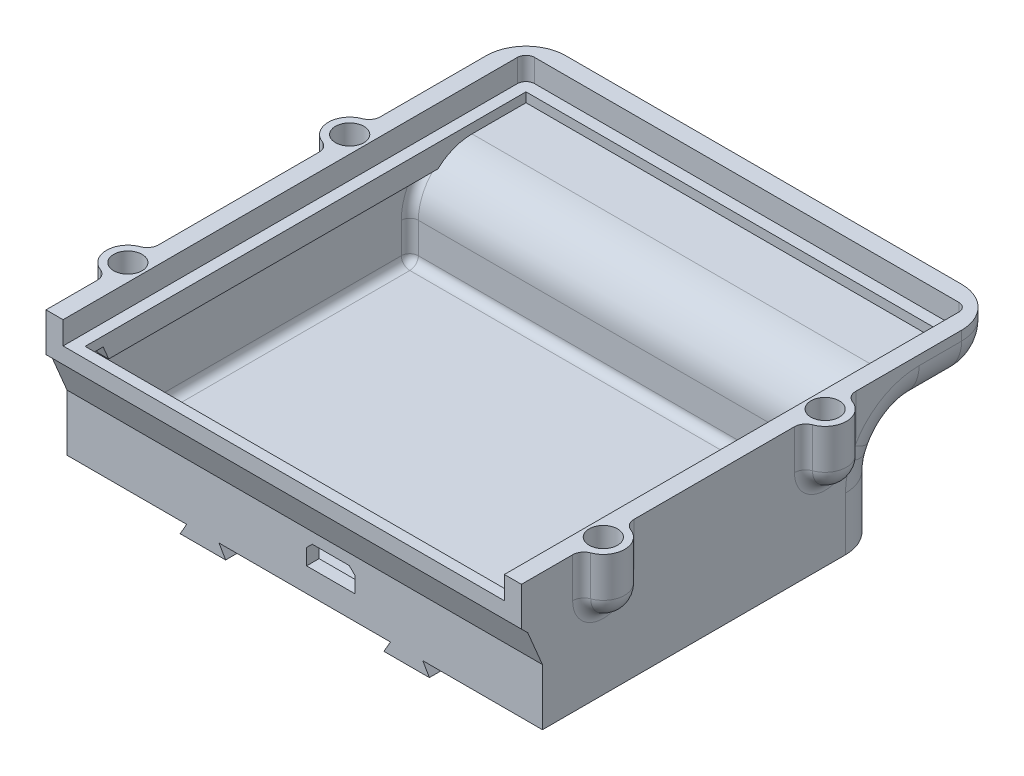
SolidWorks part; units mm, degrees
ref_plane "Front Plane" through (0, 0, 0) normal (0, 0, 1) x (1, 0, 0)
ref_plane "Top Plane" through (0, 0, 0) normal (0, 1, 0) x (1, 0, 0)
ref_plane "Right Plane" through (0, 0, 0) normal (1, 0, 0) x (0, 0, -1)
sketch "Sketch1" plane through (0, 0, 0) normal (0, 1, 0) x (1, 0, 0)
  line L4 (66, -41.25) -> (66, 44.25)
  line L5 (-66, 44.25) -> (66, 44.25)
  line L9 (-66, -41.25) -> (-66, 44.25)
  line L11 (-63, -38.25) -> (63, -38.25)
  line L12 (-66, -41.25) -> (66, -41.25)
  line L13 (-63, -38.25) -> (-63, 41.25)
  line L14 (-63, 41.25) -> (63, 41.25)
  line L15 (63, -38.25) -> (63, 41.25)
  line L16 (-63, -41.25) -> (63, 41.25) construction
  line L17 (-63, 41.25) -> (63, -41.25) construction
  line L18 (-63, -38.25) -> (63, -38.25) construction
  line L19 (-63, -41.25) -> (63, -41.25) construction
  line L20 (-66, -44.25) -> (66, -44.25) construction
  line L21 (66, -44.25) -> (66, 44.25) construction
  line L22 (63, -41.25) -> (63, 41.25) construction
  line L23 (-66, -44.25) -> (-66, 44.25) construction
  line L24 (-63, -41.25) -> (-63, 41.25) construction
  dimension "D1" = 3
  dimension "D2" = 3
  dimension "D5" = 126
  dimension "D6" = 82.5
extrude "Boss-Extrude1" add sketch "Sketch1" along normal blind 21
sketch "Sketch2" plane through (0, 0, 0) normal (0, -1, 0) x (1, 0, 0)
  line L4 (66, 41.25) -> (-66, 41.25)
  line L5 (-66, 41.25) -> (-66, -44.25)
  line L6 (-66, -44.25) -> (66, -44.25)
  line L7 (66, -44.25) -> (66, 41.25)
  line L9 (-66, 41.25) -> (-66, -44.25)
  line L10 (-66, -44.25) -> (66, -44.25)
  line L11 (66, -44.25) -> (66, 41.25)
  line L12 (66, 41.25) -> (-66, 41.25)
  dimension "D1" = 0
extrude "Boss-Extrude2" add sketch "Sketch2" along normal blind 3
sketch "Sketch3" plane through (0, 21, 0) normal (0, 1, 0) x (1, 0, 0)
  line L0 (-63, -38.25) -> (-63, -41.25)
  line L1 (-66, -41.25) -> (66, -41.25) construction
  line L2 (63, -38.25) -> (63, -41.25)
  line L3 (63, -41.25) -> (-63, -41.25)
  line L4 (-63, -38.25) -> (63, -38.25)
extrude "Cut-Extrude1" cut sketch "Sketch3" against normal blind 4
sketch "Sketch4" plane through (0, 17, 0) normal (0, 1, 0) x (1, 0, 0)
  line L0 (-61, 39.25) -> (-61, -38.25)
  line L1 (-63, 41.25) -> (63, 41.25)
  line L2 (-63, 41.25) -> (-63, -38.25)
  line L3 (-63, -38.25) -> (-61, -38.25)
  line L4 (63, 41.25) -> (63, -38.25)
  line L6 (61, 39.25) -> (61, -38.25)
  line L7 (-61, 39.25) -> (61, 39.25)
  line L8 (-61, 39.25) -> (-61, -36.25) construction
  line L9 (61, 39.25) -> (61, -36.25) construction
  line L10 (-61, -36.25) -> (61, -36.25) construction
  line L11 (61, -38.25) -> (63, -38.25)
  line L12 (-63, -38.25) -> (63, -38.25) construction
  dimension "D1" = 2
extrude "Boss-Extrude3" add sketch "Sketch4" against normal blind 4
sketch "Sketch6" plane through (0, 0, 41.25) normal (0, 0, 1) x (1, 0, 0)
  line L0 (-66, 21) -> (-66, -3) construction
  line L10 (63, 21) -> (-63, 21) construction
  line L11 (-25.5, 3.75) -> (-13.5, 3.75)
  line L12 (-25.5, 3.75) -> (-25.5, 11.25)
  line L13 (-25.5, 11.25) -> (-13.5, 11.25)
  line L14 (-13.5, 3.75) -> (-13.5, 11.25)
  line L15 (-25.5, 3.75) -> (-13.5, 11.25) construction
  line L16 (-25.5, 11.25) -> (-13.5, 3.75) construction
  line L17 (26.5, 3.75) -> (38.5, 3.75)
  line L18 (26.5, 3.75) -> (26.5, 11.25)
  line L19 (26.5, 11.25) -> (38.5, 11.25)
  line L20 (38.5, 3.75) -> (38.5, 11.25)
  line L21 (26.5, 3.75) -> (38.5, 11.25) construction
  line L22 (26.5, 11.25) -> (38.5, 3.75) construction
  line L23 (66, 21) -> (66, -3) construction
  point P11 (-19.5, 7.5)
  point P17 (32.5, 7.5)
  dimension "D1" = 12
  dimension "D2" = 7.5
  dimension "D3" = 12
  dimension "D4" = 7.5
  dimension "D5" = 46.5
  dimension "D6" = 13.5
  dimension "D7" = 13.5
  dimension "D8" = 33.5
extrude "Cut-Extrude2" cut sketch "Sketch6" against normal up to surface (3 mm away) up to face at (0, 10.75, 38.25)
sketch "Sketch7" plane through (0, 0, 41.25) normal (0, 0, 1) x (1, 0, 0)
  line L17 (0, -3) -> (0, 21) construction
  line L18 (66, -3) -> (-66, -3) construction
  line L19 (63, 21) -> (-63, 21) construction
  line L28 (-46.1132, -5) -> (-38.1132, -5)
  line L30 (-39.2679, -3) -> (-38.1132, -5)
  line L31 (-44.9585, -3) -> (-46.1132, -5)
  line L35 (39.2679, -3) -> (44.9585, -3)
  line L36 (-39.2679, -3) -> (-44.9585, -3)
  line L37 (44.9585, -3) -> (46.1132, -5)
  line L38 (39.2679, -3) -> (38.1132, -5)
  line L39 (46.1132, -5) -> (38.1132, -5)
  dimension "D1" = 8
extrude "Boss-Extrude4" add sketch "Sketch7" against normal up to surface (85.5 mm away) up to face at (0, 9, -44.25)
sketch "Sketch10" plane through (0, 21, 0) normal (0, 1, 0) x (1, 0, 0)
  line L1 (-66, -6.25) -> (66, -6.25) construction
  line L3 (0, 44.25) -> (0, -41.25) construction
  line L4 (66, 44.25) -> (-66, 44.25) construction
  line L5 (-63, -41.25) -> (63, -41.25) construction
  circle A1 centre (-66, 13.25) radius 2.5
  circle A2 centre (-66, -25.75) radius 2.5
  circle A3 centre (66, -25.75) radius 2.5
  dimension "D1" = 19.5
  dimension "D2" = 5
  dimension "D3" = 35
extrude "Cut-Extrude3" cut sketch "Sketch10" against normal blind 7
sketch "Sketch11" plane through (0, 21, 0) normal (0, 1, 0) x (1, 0, 0)
  line L0 (-66, -28.25) -> (-66, -23.25) construction
  line L1 (0, -41.25) -> (0, 44.25) construction
  line L2 (-63, -41.25) -> (63, -41.25) construction
  line L3 (66, 44.25) -> (-66, 44.25) construction
  circle A0 centre (-66, 13.25) radius 2.5
  circle A1 centre (-66, 13.25) radius 3.75
  circle A2 centre (-66, -25.75) radius 2.5
  circle A3 centre (-66, -25.75) radius 3.75
  circle A4 centre (66, -25.75) radius 3.75
  circle A5 centre (66, -25.75) radius 2.5
  dimension "D1" = 5
  dimension "D2" = 7.5
  dimension "D3" = 5
  dimension "D4" = 7.5
extrude "Boss-Extrude5" add sketch "Sketch11" against normal blind 7
sketch "Sketch13" plane through (0, 14, 0) normal (0, -1, 0) x (1, 0, 0)
  line L4 (-66, -17) -> (-66, -15.75)
  line L5 (-66, -10.75) -> (-66, -9.5)
  line L6 (-66, -17) -> (-66, -10.75)
  line L7 (-66, -10.75) -> (-66, -9.5)
  line L8 (-66, 22) -> (-66, 23.25)
  line L9 (-66, 28.25) -> (-66, 29.5)
  line L10 (-66, 22) -> (-66, 28.25)
  line L11 (-66, 28.25) -> (-66, 29.5)
  arc A4 (-66, -9.5) -> (-66, -17) centre (-66, -13.25) ccw
  arc A5 (-66, -10.75) -> (-66, -15.75) centre (-66, -13.25) ccw
  arc A6 (-66, -9.5) -> (-66, -17) centre (-66, -13.25) ccw
  arc A8 (-66, 29.5) -> (-66, 22) centre (-66, 25.75) ccw
  arc A9 (-66, 28.25) -> (-66, 23.25) centre (-66, 25.75) ccw
  arc A10 (-66, 29.5) -> (-66, 22) centre (-66, 25.75) ccw
  dimension "D1" = 0
  dimension "D2" = 0
revolve "Revolve2" add sketch "Sketch13" angle 90 about L10
sketch "Sketch14" plane through (0, 21, 0) normal (0, 1, 0) x (1, 0, 0)
  line L1 (-63, 41.25) -> (63, 41.25)
  line L2 (-63, 41.25) -> (-63, -41.25)
  line L3 (-63, -41.25) -> (63, -41.25)
  line L4 (63, 41.25) -> (63, -41.25)
extrude "Cut-Extrude4" cut sketch "Sketch14" against normal up to surface (4 mm away) up to face at (0, 17, -0.5)
sketch "Sketch17" plane through (0, 21, 0) normal (0, 1, 0) x (1, 0, 0)
  line L0 (14, 46.4113) -> (68.009, 46.4113)
  line L1 (68.009, 46.4113) -> (68.009, 34.75)
  line L4 (14, 46.4113) -> (14, 34.75)
  line L6 (14, 34.75) -> (68.009, 34.75)
extrude "Cut-Extrude5" cut sketch "Sketch17" against normal up to surface (26 mm away) up to face at (42.1132, -5, -1.5)
sketch "Sketch19" plane through (0, 14, 0) normal (0, -1, 0) x (1, 0, 0)
  line L2 (66, 23.25) -> (66, 22)
  line L3 (66, 29.5) -> (66, 28.25)
  line L4 (66, 28.25) -> (66, 22)
  line L5 (66, 29.5) -> (66, 28.25)
  arc A3 (66, 22) -> (66, 29.5) centre (66, 25.75) ccw
  arc A5 (66, 23.25) -> (66, 28.25) centre (66, 25.75) ccw
  arc A6 (66, 22) -> (66, 29.5) centre (66, 25.75) ccw
  dimension "D1" = 0
revolve "Revolve3" add sketch "Sketch19" angle 90 about L4
fillet "Fillet1" radius 2 9 edges at (66, 17.5, 22) (-66, 17.5, 22) (-66, 10.25, 25.75) (-66, 17.5, -17) (-66, 10.25, -13.25) (66, 17.5, 29.5) (-66, 17.5, 29.5) (-66, 17.5, -9.5) (66, 10.25, 25.75)
sketch "Sketch20" plane through (0, 0, 41.25) normal (0, 0, 1) x (1, 0, 0)
  line L0 (-25.5, 3.75) -> (-13.5, 3.75) construction
  line L1 (-25.5, 11.25) -> (-13.5, 11.25)
  line L2 (-25.5, 11.25) -> (-25.5, 3.75)
  line L3 (-25.5, 3.75) -> (-13.5, 3.75)
  line L4 (-13.5, 11.25) -> (-13.5, 3.75)
  line L5 (38.5, 3.75) -> (38.5, 11.25) construction
  line L6 (26.5, 11.25) -> (38.5, 11.25)
  line L7 (26.5, 11.25) -> (26.5, 3.75)
  line L8 (26.5, 3.75) -> (38.5, 3.75)
  line L9 (38.5, 11.25) -> (38.5, 3.75)
  line L16 (66, 21) -> (63, 21)
  line L17 (63, 21) -> (63, 17)
  line L18 (63, 17) -> (-63, 17)
  line L19 (-63, 17) -> (-63, 21)
  line L20 (-63, 21) -> (-66, 21)
  line L21 (-66, 21) -> (-66, -3)
  line L22 (-66, -3) -> (-44.9585, -3)
  line L23 (-44.9585, -3) -> (-46.1132, -5)
  line L24 (-46.1132, -5) -> (-38.1132, -5)
  line L25 (-38.1132, -5) -> (-39.2679, -3)
  line L26 (-39.2679, -3) -> (39.2679, -3)
  line L27 (39.2679, -3) -> (38.1132, -5)
  line L28 (38.1132, -5) -> (46.1132, -5)
  line L29 (46.1132, -5) -> (44.9585, -3)
  line L30 (44.9585, -3) -> (66, -3)
  line L31 (66, -3) -> (66, 21)
  line L32 (66, 21) -> (63, 21)
  line L33 (63, 21) -> (63, 17)
  line L34 (63, 17) -> (-63, 17)
  line L35 (-63, 17) -> (-63, 21)
  line L36 (-63, 21) -> (-66, 21)
  line L37 (-66, 21) -> (-66, -3)
  line L38 (-66, -3) -> (-44.9585, -3)
  line L39 (-44.9585, -3) -> (-46.1132, -5)
  line L40 (-46.1132, -5) -> (-38.1132, -5)
  line L41 (-38.1132, -5) -> (-39.2679, -3)
  line L42 (-39.2679, -3) -> (39.2679, -3)
  line L43 (39.2679, -3) -> (38.1132, -5)
  line L44 (38.1132, -5) -> (46.1132, -5)
  line L45 (46.1132, -5) -> (44.9585, -3)
  line L46 (44.9585, -3) -> (66, -3)
  line L47 (66, -3) -> (66, 21)
  dimension "D1" = 0
extrude "Boss-Extrude8" add sketch "Sketch20" along normal blind 2
sketch "Sketch21" plane through (0, 0, 38.25) normal (0, 0, -1) x (-1, 0, 0)
  line L1 (-38.5, 11.25) -> (-26.5, 11.25)
  line L2 (-38.5, 11.25) -> (-38.5, 3.75)
  line L3 (-38.5, 3.75) -> (-26.5, 3.75)
  line L4 (-26.5, 11.25) -> (-26.5, 3.75)
  line L5 (13.5, 11.25) -> (25.5, 11.25)
  line L6 (13.5, 11.25) -> (13.5, 3.75)
  line L7 (13.5, 3.75) -> (25.5, 3.75)
  line L8 (61, 13) -> (61, 17)
  line L9 (61, 17) -> (-61, 17)
  line L10 (-61, 17) -> (-61, 13)
  line L11 (-61, 13) -> (-63, 13)
  line L12 (-63, 13) -> (-63, 0)
  line L13 (-63, 0) -> (63, 0)
  line L14 (63, 0) -> (63, 13)
  line L15 (63, 13) -> (61, 13)
  line L16 (61, 13) -> (61, 17)
  line L17 (61, 17) -> (-61, 17)
  line L18 (-61, 17) -> (-61, 13)
  line L19 (-61, 13) -> (-63, 13)
  line L20 (-63, 13) -> (-63, 0)
  line L21 (-63, 0) -> (63, 0)
  line L22 (63, 0) -> (63, 13)
  line L23 (63, 13) -> (61, 13)
  line L24 (25.5, 11.25) -> (25.5, 3.75)
  dimension "D1" = 0
extrude "Cut-Extrude6" cut sketch "Sketch21" against normal blind 2
sketch "Sketch22" plane through (0, 0, -34.75) normal (0, 0, -1) x (-1, 0, 0)
  line L1 (-14, -12.775) -> (-80.2268, -12.775)
  line L2 (-14, -12.775) -> (-14, 29.6079)
  line L3 (-14, 29.6079) -> (-80.2268, 29.6079)
  line L4 (-80.2268, -12.775) -> (-80.2268, 29.6079)
extrude "Cut-Extrude7" cut sketch "Sketch22" against normal blind 90
sketch "Sketch23" plane through (0, 0, 43.25) normal (0, 0, 1) x (1, 0, 0)
  line L3 (-24.2, 25.8287) -> (18.3425, 25.8287)
  line L4 (-24.2, 25.8287) -> (-24.2, -6.6902)
  line L5 (-24.2, -6.6902) -> (18.3425, -6.6902)
  line L6 (18.3425, 25.8287) -> (18.3425, -6.6902)
  dimension "D1" = 38.8
extrude "Cut-Extrude8" cut sketch "Sketch23" against normal blind 90
mirror "Mirror1" about plane through (-24.2, 25.8287, -46.75) normal (-1, 0, 0) of bodies 119
sketch "Sketch28" plane through (-25.5, 0, 0) normal (1, 0, 0) x (0, 0, -1)
  line L4 (-43.25, 3.75) -> (-40.25, 3.75)
  line L5 (-40.25, 3.75) -> (-40.25, 11.25)
  line L6 (-40.25, 11.25) -> (-43.25, 11.25)
  line L7 (-43.25, 11.25) -> (-43.25, 3.75)
  line L8 (-43.25, 3.75) -> (-40.25, 3.75)
  line L9 (-40.25, 3.75) -> (-40.25, 11.25)
  line L10 (-40.25, 11.25) -> (-43.25, 11.25)
  line L11 (-43.25, 11.25) -> (-43.25, 3.75)
  dimension "D1" = 0
extrude "Boss-Extrude11" add sketch "Sketch28" along normal up to surface (2.6 mm away) up to face at (-22.9, 7.5, 41.75)
sketch "Sketch24" plane through (0, 17, 0) normal (0, 1, 0) x (1, 0, 0)
  line L0 (14.6, -43.25) -> (17.6, -43.25) construction
  line L1 (-63.1909, -40.75) -> (14.6, -40.75)
  line L2 (-63.1909, -40.75) -> (-63.1909, -43.25)
  line L3 (-63.1909, -43.25) -> (14.6, -43.25)
  line L4 (14.6, -40.75) -> (14.6, -43.25)
  line L5 (14.6, 41.25) -> (14.6, -43.25) construction
  dimension "D1" = 2.5
extrude "Boss-Extrude9" add sketch "Sketch24" along normal up to surface (4 mm away) up to face at (-24.2, 21, 4.25)
sketch "Sketch26" plane through (0, 0, 40.25) normal (0, 0, -1) x (-1, 0, 0)
  line L0 (61, 17) -> (-12.6, 17) construction
  line L1 (-12.6, 13) -> (61, 13)
  line L2 (-12.6, 13) -> (-12.6, 17)
  line L3 (-12.6, 17) -> (61, 17)
  line L4 (61, 13) -> (61, 17)
extrude "Boss-Extrude10" add sketch "Sketch26" along normal blind 1
sketch "Sketch27" plane through (0, 0, 43.25) normal (0, 0, 1) x (1, 0, 0)
  line L0 (-23.8777, 5.02) -> (-15.3724, 5.02)
  line L1 (-23.8777, 5.02) -> (-23.8777, 1.22)
  line L2 (-23.8777, 1.22) -> (-15.3724, 1.22)
  line L3 (-15.3724, 5.02) -> (-15.3724, 1.22)
  line L4 (-66, 21) -> (-66, -3) construction
  line L5 (-39.2679, -3) -> (-9.1321, -3) construction
  point P0 (17.6, -3)
  point P5 (17.6, -3)
  dimension "D1" = 3.8
  dimension "D2" = 8.5054
  dimension "D3" = 42.1223
  dimension "D4" = 4.22
extrude "Cut-Extrude9" cut sketch "Sketch27" against normal blind 3
chamfer "Chamfer1" distance 1 angle 45 2 edges at (-23.8777, 5.02, 41.75) (-15.3724, 5.02, 41.75)
sketch "Sketch31" plane through (0, 0, 40.25) normal (0, 0, -1) x (-1, 0, 0)
  line L0 (15.3724, 1.22) -> (15.3724, 4.02)
  line L1 (15.3724, 4.02) -> (16.3724, 5.02)
  line L2 (16.3724, 5.02) -> (22.8777, 5.02)
  line L3 (22.8777, 5.02) -> (23.8777, 4.02)
  line L4 (63, 13) -> (-14.6, 13)
  line L5 (-14.6, 13) -> (-14.6, 0)
  line L6 (-14.6, 0) -> (63, 0)
  line L7 (63, 0) -> (63, 13)
  line L8 (63, 13) -> (-14.6, 13)
  line L9 (-14.6, 13) -> (-14.6, 0)
  line L10 (-14.6, 0) -> (63, 0)
  line L11 (63, 0) -> (63, 13)
  line L12 (23.8777, 4.02) -> (23.8777, 1.22)
  line L13 (23.8777, 1.22) -> (15.3724, 1.22)
  dimension "D1" = 0
extrude "Boss-Extrude13" add sketch "Sketch31" along normal blind 6
sketch "Sketch29" plane through (0, 0, 43.25) normal (0, 0, 1) x (1, 0, 0)
  line L3 (-66, 10) -> (17.6, 10)
  line L17 (17.6, -3) -> (17.6, 21)
  line L18 (17.6, 21) -> (-66, 21)
  line L19 (-66, 21) -> (-66, -3)
  line L20 (-66, -3) -> (-44.9585, -3)
  line L21 (-44.9585, -3) -> (-46.1132, -5)
  line L22 (-46.1132, -5) -> (-38.1132, -5)
  line L23 (-38.1132, -5) -> (-39.2679, -3)
  line L24 (-39.2679, -3) -> (-9.1321, -3)
  line L25 (-9.1321, -3) -> (-10.2868, -5)
  line L26 (-10.2868, -5) -> (-2.2868, -5)
  line L27 (-2.2868, -5) -> (-3.4415, -3)
  line L28 (-3.4415, -3) -> (17.6, -3)
  line L29 (17.6, -3) -> (17.6, 10)
  line L31 (-66, 10) -> (-66, -3)
  line L32 (-66, -3) -> (-44.9585, -3)
  line L33 (-44.9585, -3) -> (-46.1132, -5)
  line L34 (-46.1132, -5) -> (-38.1132, -5)
  line L35 (-38.1132, -5) -> (-39.2679, -3)
  line L36 (-39.2679, -3) -> (-9.1321, -3)
  line L37 (-9.1321, -3) -> (-10.2868, -5)
  line L38 (-10.2868, -5) -> (-2.2868, -5)
  line L39 (-2.2868, -5) -> (-3.4415, -3)
  line L40 (-3.4415, -3) -> (17.6, -3)
  dimension "D1" = 13
  dimension "D2" = 0
extrude "Cut-Extrude10" cut sketch "Sketch29" against normal blind 6.8
chamfer "Chamfer3" distance 4 angle 45 1 edges at (-24.2, 10, 36.45)
sketch "Sketch32" plane through (0, 0, 0) normal (0, 1, 0) x (1, 0, 0)
  line L4 (-63, 41.25) -> (-63, -34.25)
  line L5 (-63, -34.25) -> (14.6, -34.25)
  line L6 (14.6, -34.25) -> (14.6, 41.25)
  line L7 (14.6, 41.25) -> (-63, 41.25)
  line L8 (-63, 41.25) -> (-63, -34.25)
  line L9 (-63, -34.25) -> (14.6, -34.25)
  line L10 (14.6, -34.25) -> (14.6, 41.25)
  line L11 (14.6, 41.25) -> (-63, 41.25)
  dimension "D1" = 0
extrude "Cut-Extrude11" cut sketch "Sketch32" against normal blind 0.5
sketch "Sketch33" plane through (-66, 0, 0) normal (-1, 0, 0) x (0, 0, 1)
  line L0 (43.25, 9.08) -> (40.15, 9.08)
  line L1 (43.25, 9.08) -> (43.25, 21)
  line L2 (43.25, 21) -> (40.15, 21)
  line L3 (40.15, 9.08) -> (40.15, 21)
  dimension "D1" = 3.1
extrude "Cut-Extrude12" cut sketch "Sketch33" against normal up to surface (83.6 mm away) up to face at (17.6, 12.7479, 10.7567)
sketch "Sketch35" plane through (-66, 0, 0) normal (-1, 0, 0) x (0, 0, 1)
  line L0 (-44.25, 15.3333) -> (-29.765, 15.3333)
  line L1 (-20.8278, -5) -> (-20.8278, 6.3961)
  line L2 (-44.25, 15.3333) -> (-44.25, -5)
  line L3 (-44.25, -5) -> (-20.8278, -5)
  arc A0 (-20.8278, 6.3961) -> (-29.765, 15.3333) centre (-29.765, 6.3961) ccw
  point P3 (-44.25, -5)
  point P6 (-44.25, -5)
extrude "Cut-Extrude13" cut sketch "Sketch35" against normal up to surface (83.6 mm away) up to face at (17.6, 12.9227, 8.1929)
sketch "Sketch36" plane through (-66, 0, 0) normal (-1, 0, 0) x (0, 0, 1)
  line L0 (-44.25, 15.3333) -> (-29.765, 15.3333)
  line L1 (-20.8278, -3) -> (-20.8278, 6.3961)
  line L2 (-23.8278, -3) -> (-23.8278, 6.3961)
  line L3 (-44.25, 12.3333) -> (-29.765, 12.3333)
  line L5 (-44.25, 15.3333) -> (-44.25, 12.3333)
  line L6 (-20.8278, -3) -> (-23.8278, -3)
  line L7 (-23.8278, -4.3465) -> (-23.8278, 6.3961) construction
  line L8 (-20.8278, -4.3465) -> (-20.8278, 6.3961) construction
  arc A0 (-20.8278, 6.3961) -> (-29.765, 15.3333) centre (-29.765, 6.3961) ccw
  arc A1 (-23.8278, 6.3961) -> (-29.765, 12.3333) centre (-29.765, 6.3961) ccw
  dimension "D1" = 3
extrude "Boss-Extrude15" add sketch "Sketch36" against normal up to surface (83.6 mm away) up to face at (17.6, 12.9313, 2.6547)
fillet "Fillet2" radius 7 8 edges at (-66, 16.6666, -44.25) (17.6, 16.6666, -44.25) (17.6, 1.698, -23.8278) (17.6, 12.3333, -37.0075) (-66, 12.3333, -37.0075) (-66, 1.698, -23.8278) (17.6, 10.5943, -25.5668) (-66, 10.5943, -25.5668)
sketch "Sketch37" plane through (0, 0, -20.8278) normal (0, 0, -1) x (-1, 0, 0)
  line L4 (46.1132, -5) -> (44.9585, -3)
  line L5 (44.9585, -3) -> (39.2679, -3)
  line L6 (39.2679, -3) -> (38.1132, -5)
  line L7 (38.1132, -5) -> (46.1132, -5)
  line L8 (46.1132, -5) -> (44.9585, -3)
  line L9 (44.9585, -3) -> (39.2679, -3)
  line L10 (39.2679, -3) -> (38.1132, -5)
  line L11 (38.1132, -5) -> (46.1132, -5)
  line L12 (10.2868, -5) -> (9.1321, -3)
  line L13 (9.1321, -3) -> (3.4415, -3)
  line L14 (3.4415, -3) -> (2.2868, -5)
  line L15 (2.2868, -5) -> (10.2868, -5)
  line L16 (10.2868, -5) -> (9.1321, -3)
  line L17 (9.1321, -3) -> (3.4415, -3)
  line L18 (3.4415, -3) -> (2.2868, -5)
  line L19 (2.2868, -5) -> (10.2868, -5)
  dimension "D1" = 0
  dimension "D2" = 0
extrude "Boss-Extrude16" add sketch "Sketch37" along normal up to surface (3 mm away) up to face at (-24.2, 1.698, -23.8278)
fillet "Fillet5" radius 7 3 edges at (15.5497, 14.3835, -42.1997) (-63.9497, 14.3835, -42.1997) (-24.2, 12.3333, -44.25)
sketch "Sketch38" plane through (17.6, 0, 0) normal (1, 0, 0) x (0, 0, -1)
  line L0 (-40.15, 14.18) -> (-36.45, 10.48)
  line L3 (-36.45, 6) -> (-40.15, 9.7)
  line L4 (-40.15, 9.7) -> (-40.15, 14.18)
  line L5 (-36.45, 6) -> (-36.45, 10.48)
extrude "Cut-Extrude14" cut sketch "Sketch38" against normal up to surface (83.6 mm away) up to face at (-66, 18.1556, -26.5308)
sketch "Sketch39" plane through (0, -12.985, 12.985) normal (0, -0.7071, 0.7071) x (1, 0, 0)
  line L8 (-66, 38.4171) -> (-66, 33.1845)
  line L9 (-66, 33.1845) -> (17.6, 33.1845)
  line L10 (17.6, 33.1845) -> (17.6, 38.4171)
  line L11 (17.6, 38.4171) -> (-66, 38.4171)
  line L12 (-66, 38.4171) -> (-66, 33.1845)
  line L13 (-66, 33.1845) -> (17.6, 33.1845)
  line L14 (17.6, 33.1845) -> (17.6, 38.4171)
  line L15 (17.6, 38.4171) -> (-66, 38.4171)
  dimension "D1" = 0
extrude "Boss-Extrude17" add sketch "Sketch39" against normal blind 2
sketch "Sketch40" plane through (0, 17, 0) normal (0, 1, 0) x (1, 0, 0)
  line L1 (-63, -40.15) -> (14.6, -40.15)
  line L2 (-63, -40.15) -> (-63, -38.2752)
  line L3 (-63, -38.2752) -> (14.6, -38.2752)
  line L4 (14.6, -40.15) -> (14.6, -38.2752)
extrude "Boss-Extrude18" add sketch "Sketch40" against normal blind 2.5
sketch "Sketch41" plane through (14.6, 0, 0) normal (-1, 0, 0) x (0, 0, 1)
  line L1 (38.3568, 15.3275) -> (34.25, 5.5676)
  line L4 (35.102, 15.3275) -> (31.4848, 6.7311)
  line L5 (38.3568, 15.3275) -> (35.102, 15.3275)
  line L6 (34.25, 5.5676) -> (31.4848, 6.7311)
  line L7 (35.5916, 16.491) -> (31.4848, 6.7311) construction
  dimension "D1" = 3
extrude "Cut-Extrude15" cut sketch "Sketch41" along normal up to surface (77.6 mm away) up to face at (-63, 6.3407, 0.7595)
fillet "Fillet3" radius 1.5 12 edges at (-24.2, -0.5, 34.25) (-63, -0.5, 6.7111) (14.6, -0.5, 6.7111) (-63, 19, -41.25) (-63, 2.5338, 34.25) (14.6, 2.5338, 34.25) (14.6, 19, -41.25) (14.6, 10.0055, -21.5891) (-63, 10.0055, -21.5891) (14.6, 2.948, -20.8278) (-63, 2.948, -20.8278) (-24.2, -0.5, -20.8278)
sketch "Sketch45" plane through (0, -11.4063, 27.1078) normal (0, 0.3878, -0.9217) x (-1, 0, 0)
  line L4 (63, 29.0041) -> (-14.6, 29.0041)
  line L5 (-14.6, 29.0041) -> (-14.6, 14.5477)
  line L6 (-13.1, 18.4153) -> (61.5, 18.4153)
  line L7 (63, 14.5477) -> (63, 29.0041)
  line L8 (63, 29.0041) -> (-14.6, 29.0041)
  line L9 (-14.6, 29.0041) -> (-14.6, 14.5477)
  line L10 (-13.1, 18.4153) -> (61.5, 18.4153)
  line L11 (63, 14.5477) -> (63, 29.0041)
  ellipse E2 centre (-13.1, 14.5477) end of major axis (-13.1, 18.4153) minor radius 1.5 (-13.1, 18.4153) -> (-14.6, 14.5477) ccw
  ellipse E3 centre (61.5, 14.5477) end of major axis (61.5, 10.6802) minor radius 1.5 (63, 14.5477) -> (61.5, 18.4153) ccw
  ellipse E4 centre (-13.1, 14.5477) end of major axis (-13.1, 18.4153) minor radius 1.5 (-13.1, 18.4153) -> (-14.6, 14.5477) ccw
  ellipse E5 centre (61.5, 14.5477) end of major axis (61.5, 10.6802) minor radius 1.5 (63, 14.5477) -> (61.5, 18.4153) ccw
  dimension "D1" = 0
extrude "Boss-Extrude28" add sketch "Sketch45" against normal blind 1.5
sketch "Sketch46" plane through (17.6, 0, 0) normal (1, 0, 0) x (0, 0, -1)
  line L3 (-36.45, 10.48) -> (-39.03, 13.06)
  line L4 (-39.03, 13.06) -> (-36.45, 6.9284)
  line L5 (-36.45, 6.9284) -> (-36.45, 10.48)
  line L6 (-36.45, 10.48) -> (-39.03, 13.06)
  line L7 (-39.03, 13.06) -> (-36.45, 6.9284)
  line L8 (-36.45, 6.9284) -> (-36.45, 10.48)
  dimension "D1" = 0
extrude "Boss-Extrude29" add sketch "Sketch46" against normal up to surface (83.6 mm away) up to face at (-66, 18.1556, -26.5308)
